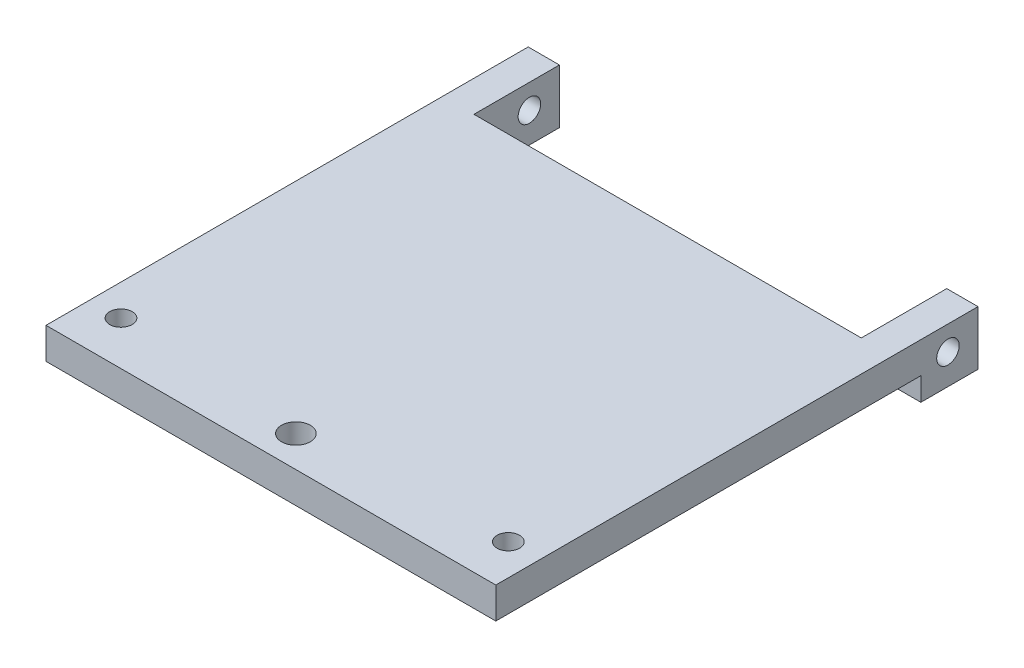
SolidWorks part; units mm, degrees
ref_plane "Front" through (0, 0, 0) normal (0, 0, 1) x (1, 0, 0)
ref_plane "Top" through (0, 0, 0) normal (0, 1, 0) x (1, 0, 0)
ref_plane "Right" through (0, 0, 0) normal (1, 0, 0) x (0, 0, -1)
sketch "Sketch1" plane through (0, 0, 0) normal (0, 1, 0) x (1, 0, 0)
  line L1 (0, 0) -> (72, 0)
  line L2 (0, 0) -> (0, -47)
  line L3 (0, -47) -> (72, -47)
  line L4 (72, 0) -> (72, -47)
  line L5 (0, 0) -> (5, 0)
  line L6 (0, 0) -> (0, 13)
  line L7 (0, 13) -> (5, 13)
  line L8 (5, 0) -> (5, 13)
  line L9 (72, 0) -> (67, 0)
  line L10 (72, 0) -> (72, 13.6822)
  line L11 (72, 13.6822) -> (67, 13.6822)
  line L12 (67, 0) -> (67, 13.6822)
  dimension "D1" = 5
  dimension "D2" = 5
  dimension "D3" = 72
  dimension "D4" = 60
  dimension "D5" = 13
extrude "Boss-Extrude1" add sketch "Sketch1" along normal blind 5 contours L4 L1 L2 L3 | L12 L1 L10 L11 | L6 L7 L8 L5 region at (36, 0, 23.5) region at (69.5, 0, -6.8411)
sketch "Sketch3" plane through (72, 0, 0) normal (1, 0, 0) x (0, 0, -1)
  line L0 (-0.2921, 5.9295) -> (-0.0426, -1.3663) construction
  line L1 (13.6822, 5) -> (0.037, 5)
  line L2 (13.6822, 5) -> (13.6822, -3.6945)
  line L3 (13.6822, -3.6945) -> (0.037, -3.6945)
  line L4 (0.037, 5) -> (0.037, -3.6945)
extrude "Boss-Extrude3" add sketch "Sketch3" against normal blind 5
sketch "Sketch5" plane through (0, 0, 0) normal (-1, 0, 0) x (0, 0, 1)
  line L1 (-13.6822, 5) -> (-0.037, 5)
  line L2 (-13.6822, 5) -> (-13.6822, -3.6945)
  line L3 (-13.6822, -3.6945) -> (-0.037, -3.6945)
  line L4 (-0.037, 5) -> (-0.037, -3.6945)
extrude "Boss-Extrude4" add sketch "Sketch5" against normal blind 5
sketch "Sketch6" plane through (0, 0, 47) normal (0, 0, 1) x (1, 0, 0)
  line L1 (0, 0) -> (72, 0)
  line L2 (0, 0) -> (0, 5)
  line L3 (0, 5) -> (72, 5)
  line L4 (72, 0) -> (72, 5)
extrude "Boss-Extrude5" add sketch "Sketch6" along normal blind 21
sketch "Sketch8" plane through (0, 0, -13.6822) normal (0, 0, -1) x (-1, 0, 0)
  line L1 (16.5962, 20.9729) -> (-97.8892, 20.9729)
  line L2 (16.5962, 20.9729) -> (16.5962, -24.1683)
  line L3 (16.5962, -24.1683) -> (-97.8892, -24.1683)
  line L4 (-97.8892, 20.9729) -> (-97.8892, -24.1683)
extrude "Cut-Extrude2" cut sketch "Sketch8" against normal blind 4.5
sketch "Sketch9" plane through (0, 0, 0) normal (0, 0, -1) x (-1, 0, 0)
  line L1 (-5, 5) -> (-67, 5)
  line L2 (-5, 5) -> (-5, 0)
  line L3 (-5, 0) -> (-67, 0)
  line L4 (-67, 5) -> (-67, 0)
extrude "Cut-Extrude3" cut sketch "Sketch9" against normal blind 4.5
sketch "Sketch10" plane through (0, 0, 0) normal (0, -1, 0) x (-1, 0, 0)
  line L0 (0, 0.037) -> (0, -68) construction
  line L1 (0, -68) -> (-72, -68) construction
  line L2 (-72, 0.037) -> (-72, -68) construction
  circle A0 centre (-35, -63) radius 2.3
  circle A1 centre (-67, -61) radius 1.8
  circle A2 centre (-5, -61) radius 1.8
  dimension "D1" = 35
  dimension "D3" = 5
  dimension "D4" = 7
  dimension "D5" = 5
  dimension "D6" = 7
  dimension "D2" = 5
extrude "Cut-Extrude4" cut sketch "Sketch10" against normal blind 10
sketch "Sketch11" plane through (72, 0, 0) normal (1, 0, 0) x (0, 0, -1)
  circle A0 centre (4.375, 1.118) radius 1.8
extrude "Cut-Extrude5" cut sketch "Sketch11" against normal blind 90
